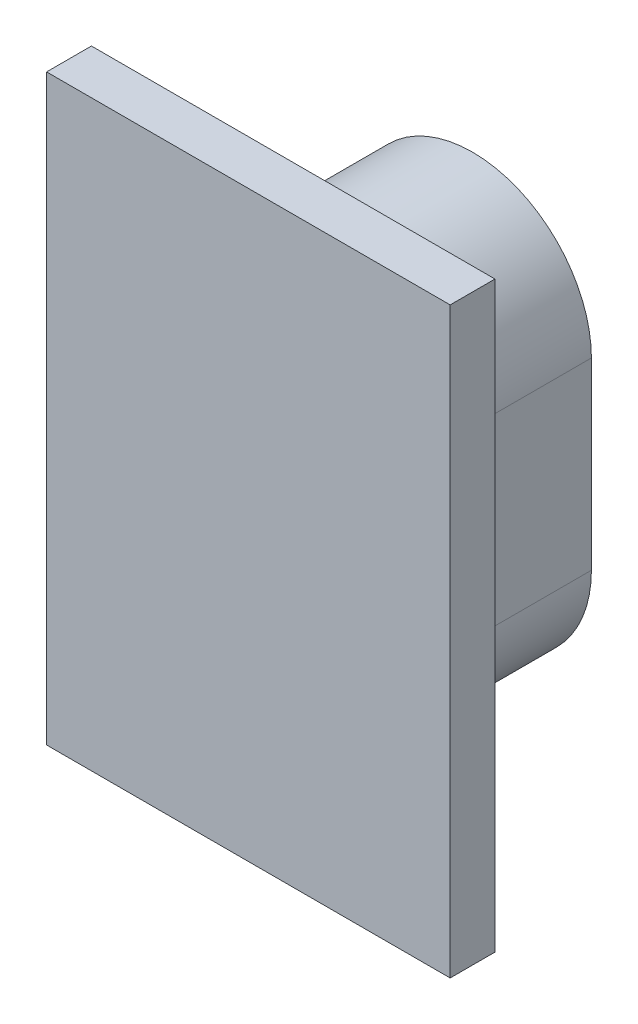
SolidWorks part; units mm, degrees
ref_plane "Front Plane" through (0, 0, 0) normal (0, 0, 1) x (1, 0, 0)
ref_plane "Top Plane" through (0, 0, 0) normal (0, 1, 0) x (1, 0, 0)
ref_plane "Right Plane" through (0, 0, 0) normal (1, 0, 0) x (0, 0, -1)
sketch "Sketch1" plane through (0, 0, 0) normal (0, 0, 1) x (1, 0, 0)
  line L1 (-19.6138, 16.2133) -> (25.3862, 16.2133)
  line L2 (-19.6138, 16.2133) -> (-19.6138, -48.7867)
  line L3 (-19.6138, -48.7867) -> (25.3862, -48.7867)
  line L4 (25.3862, 16.2133) -> (25.3862, -48.7867)
  dimension "D1" = 45
  dimension "D2" = 65
extrude "Boss-Extrude1" add sketch "Sketch1" along normal blind 5
sketch "Sketch4" plane through (0, 0, 0) normal (0, 0, -1) x (-1, 0, 0)
  line L0 (-2.8862, -28.7867) -> (-2.8862, 49971.2133) construction
  line L3 (19.6138, -48.7867) -> (-25.3862, -48.7867) construction
  line L4 (-15.3862, -16.2867) -> (49984.6138, -16.2867) construction
  line L5 (-25.3862, -48.7867) -> (-25.3862, 16.2133) construction
  line L6 (-2.8862, -6.0367) -> (-2.8862, -26.5367) construction
  line L7 (10.3638, -6.0367) -> (10.3638, -26.5367)
  line L8 (-16.1362, -6.0367) -> (-16.1362, -26.5367)
  line L9 (7.8638, -6.0367) -> (7.8638, -26.5367)
  line L10 (-13.6362, -6.0367) -> (-13.6362, -26.5367)
  arc A0 (10.3638, -6.0367) -> (-16.1362, -6.0367) centre (-2.8862, -6.0367) ccw
  arc A1 (-16.1362, -26.5367) -> (10.3638, -26.5367) centre (-2.8862, -26.5367) ccw
  arc A2 (-13.6362, -26.5367) -> (7.8638, -26.5367) centre (-2.8862, -26.5367) ccw
  arc A3 (7.8638, -6.0367) -> (-13.6362, -6.0367) centre (-2.8862, -6.0367) ccw
  point P4 (-2.8862, -48.7867)
  point P9 (-25.3862, -16.2867)
  point P12 (-2.8862, -16.2867)
  dimension "D1" = 2.5
extrude "Boss-Extrude2" add sketch "Sketch4" along normal blind 20
